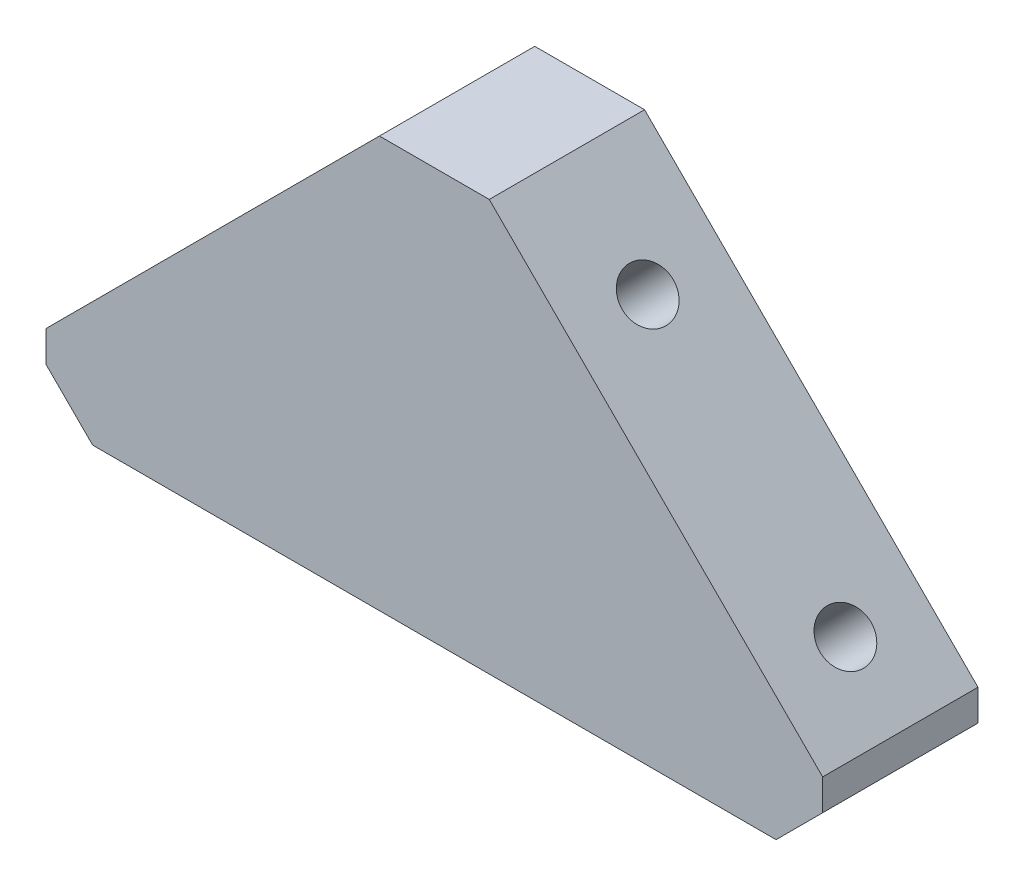
SolidWorks part; units mm, degrees
ref_plane "Front" through (0, 0, 0) normal (0, 0, 1) x (1, 0, 0)
ref_plane "Top" through (0, 0, 0) normal (0, 1, 0) x (1, 0, 0)
ref_plane "Right" through (0, 0, 0) normal (1, 0, 0) x (0, 0, -1)
sketch "Esquisse1" plane through (0, 0, 0) normal (0, 0, 1) x (1, 0, 0)
  line L0 (-25, 0) -> (25, 0)
  line L1 (25, 0) -> (25, 5)
  line L2 (25, 5) -> (0, 30)
  line L3 (0, 30) -> (0, 0) construction
  line L4 (-25, 5) -> (0, 30)
  line L5 (-25, 0) -> (-25, 5)
  point P5 (25, 2.5)
  dimension "D1" = 50
  dimension "D2" = 45
  dimension "D3" = 5
extrude "Boss.-Extru.1" add sketch "Esquisse1" along normal blind 10
sketch "Esquisse2" plane through (15, 15, 0) normal (0.7071, 0.7071, 0) x (0, 0, -1)
  line L0 (-5, -14.1421) -> (-5, 21.2132) construction
  line L1 (-10, -14.1421) -> (0, -14.1421) construction
  line L2 (-10, 21.2132) -> (0, 21.2132) construction
  circle A0 centre (-5, 8.8579) radius 1.65
  circle A1 centre (-5, -9.1421) radius 1.65
  dimension "D1" = 18
  dimension "D2" = 3.3
  dimension "D3" = 5
extrude "Enlèv. mat.-Extru.1" cut sketch "Esquisse2" against normal blind 8
sketch "Esquisse3" plane through (-15, 15, 0) normal (-0.7071, 0.7071, 0) x (0, 0, 1)
  line L0 (5, -14.1421) -> (5, 21.2132) construction
  line L1 (10, -14.1421) -> (0, -14.1421) construction
  line L2 (10, 21.2132) -> (0, 21.2132) construction
  circle A0 centre (5, 9.8579) radius 1.65
  circle A1 centre (5, -8.1421) radius 1.65
  dimension "D1" = 18
  dimension "D2" = 3.3
  dimension "D3" = 6
extrude "Enlèv. mat.-Extru.2" cut sketch "Esquisse3" against normal blind 8
chamfer "Chanfrein1" distance 5 angle 45 1 edges at (0, 30, 5)
sketch "Esquisse4" plane through (0, 0, 0) normal (0, -1, 0) x (1, 0, 0)
  line L0 (-25, 5) -> (25, 5) construction
  line L1 (-25, 10) -> (-25, 0) construction
  line L2 (25, 10) -> (25, 0) construction
  line L3 (0, 5) -> (0, 8.5239) construction
  circle A0 centre (0, 5) radius 1.65
  circle A1 centre (-16, 5) radius 1.65
  circle A2 centre (16, 5) radius 1.65
  dimension "D1" = 3.3
  dimension "D2" = 16
extrude "Enlèv. mat.-Extru.3" cut sketch "Esquisse4" against normal blind 10
chamfer "Chanfrein3" distance 3 angle 45 2 edges at (25, 0, 5) (-25, 0, 5)
